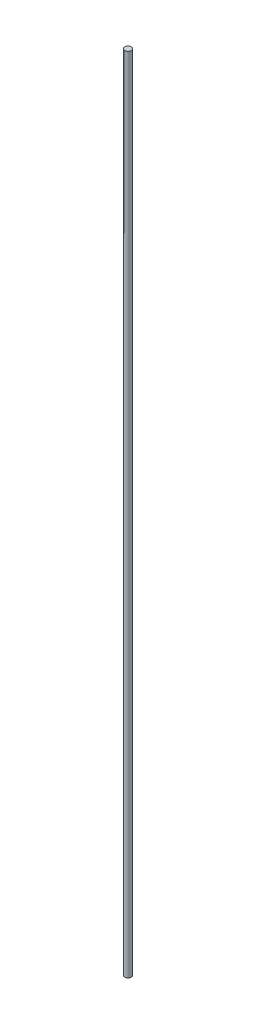
SolidWorks part; units mm, degrees
ref_plane "Front Plane" through (0, 0, 0) normal (0, 0, 1) x (1, 0, 0)
ref_plane "Top Plane" through (0, 0, 0) normal (0, 1, 0) x (1, 0, 0)
ref_plane "Right Plane" through (0, 0, 0) normal (1, 0, 0) x (0, 0, -1)
sketch "Sketch1" plane through (0, 0, 0) normal (0, 1, 0) x (1, 0, 0)
  circle A0 centre (0, 0) radius 5.08
extrude "Boss-Extrude1" add sketch "Sketch1" along normal blind 1244.6
